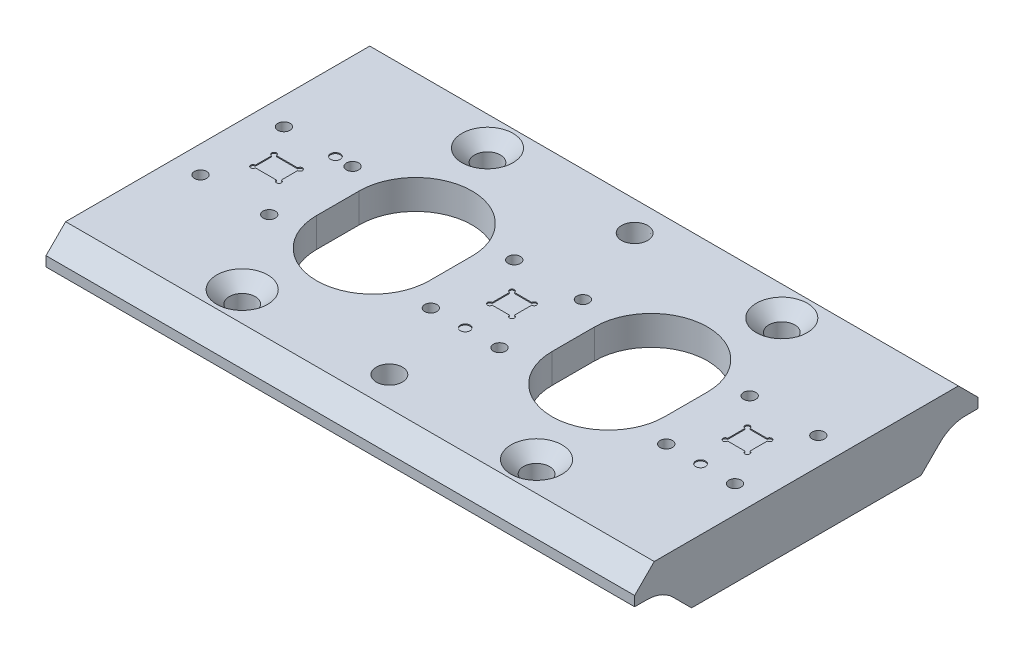
SolidWorks part; units mm, degrees
material "6061 Сплав"
ref_plane "Спереди" through (0, 0, 0) normal (0, 0, 1) x (1, 0, 0)
ref_plane "Сверху" through (0, 0, 0) normal (0, 1, 0) x (1, 0, 0)
ref_plane "Справа" through (0, 0, 0) normal (1, 0, 0) x (0, 0, -1)
sketch "Эскиз5" plane through (0, 0, 0) normal (0, 1, 0) x (1, 0, 0)
  line L1 (0, -35) -> (120, -35)
  line L2 (0, -35) -> (0, 35)
  line L3 (0, 35) -> (120, 35)
  line L4 (120, -35) -> (120, 35)
  line L5 (0, -35) -> (120, 35) construction
  line L6 (0, 35) -> (120, -35) construction
  point P0 (0, 0)
  point P5 (0, 0)
extrude "Бобышка-Вытянуть2" add sketch "Эскиз5" against normal blind 6
ref_axis "Ось1" through (120, 0, 0) along (-1, 0, 0)
sketch "Sketch1" plane through (0, 0, 0) normal (0, 1, 0) x (1, 0, 0)
  line L0 (9.86, -2.16) -> (14.14, -2.16)
  line L1 (9.36, -1.66) -> (9.36, 1.66)
  line L2 (9.86, 2.16) -> (14.14, 2.16)
  line L3 (14.64, -1.66) -> (14.64, 1.66)
  line L4 (9.36, -2.16) -> (14.64, 2.16) construction
  line L5 (9.36, 2.16) -> (14.64, -2.16) construction
  circle A0 centre (16, 8) radius 1
  arc A1 (14.64, 1.66) -> (14.14, 2.16) centre (14.64, 2.16) ccw
  arc A2 (9.86, 2.16) -> (9.36, 1.66) centre (9.36, 2.16) ccw
  arc A3 (9.36, -1.66) -> (9.86, -2.16) centre (9.36, -2.16) ccw
  arc A4 (14.14, -2.16) -> (14.64, -1.66) centre (14.64, -2.16) ccw
  point P0 (0, 0)
  point P1 (12, 0)
  point P2 (12, 0)
  point P9 (5.5, 8)
  point P10 (19.5, 8)
  point P11 (19.5, -9)
  point P12 (5.5, -9)
  dimension "D11" = 5.28
  dimension "D1" = 8
  dimension "D2" = 9
  dimension "D3" = 6.5
  dimension "D4" = 7.5
  dimension "D5" = 6.5
  dimension "D6" = 7.5
  dimension "D7" = 9
  dimension "D8" = 8
  dimension "D9" = 3.5
  dimension "D10" = 8
  dimension "D12" = 4.32
sketch "Sketch2" plane through (0, 0, 0) normal (0, 1, 0) x (1, 0, 0)
  line L0 (24, 35) -> (24, -35) construction
  line L1 (57.74, 1.76) -> (57.74, -1.76)
  line L2 (58.24, 2.26) -> (61.76, 2.26)
  line L3 (62.26, 1.76) -> (62.26, -1.76)
  line L4 (58.24, -2.26) -> (61.76, -2.26)
  line L5 (57.74, 2.26) -> (62.26, -2.26) construction
  line L6 (62.26, 2.26) -> (57.74, -2.26) construction
  line L7 (0, 35) -> (120, 35) construction
  line L8 (0, -35) -> (120, -35) construction
  line L12 (105.74, 1.76) -> (105.74, -1.76)
  line L13 (106.24, 2.26) -> (109.76, 2.26)
  line L14 (110.26, 1.76) -> (110.26, -1.76)
  line L15 (106.24, -2.26) -> (109.76, -2.26)
  line L16 (105.74, 2.26) -> (110.26, -2.26) construction
  line L17 (110.26, 2.26) -> (105.74, -2.26) construction
  circle A0 centre (59.481, -9.027) radius 1
  arc A1 (62.26, 1.76) -> (61.76, 2.26) centre (62.26, 2.26) ccw
  circle A2 centre (107.481, -9.027) radius 1
  arc A3 (58.24, 2.26) -> (57.74, 1.76) centre (57.74, 2.26) ccw
  arc A4 (57.74, -1.76) -> (58.24, -2.26) centre (57.74, -2.26) ccw
  arc A5 (61.76, -2.26) -> (62.26, -1.76) centre (62.26, -2.26) ccw
  arc A6 (110.26, 1.76) -> (109.76, 2.26) centre (110.26, 2.26) ccw
  arc A7 (109.76, -2.26) -> (110.26, -1.76) centre (110.26, -2.26) ccw
  arc A8 (105.74, -1.76) -> (106.24, -2.26) centre (105.74, -2.26) ccw
  arc A9 (106.24, 2.26) -> (105.74, 1.76) centre (105.74, 2.26) ccw
  point P0 (60, 0)
  point P1 (60, 0)
  point P5 (60, 0)
  point P6 (60, 0)
  point P7 (59.481, -9.027)
  point P8 (66.481, -9.027)
  point P9 (52.481, -9.027)
  point P10 (52.481, 7.973)
  point P11 (66.481, 7.973)
  point P31 (108, 0)
  point P32 (108, 0)
  point P36 (108, 0)
  point P37 (108, 0)
  point P38 (107.481, -9.027)
  point P39 (114.481, -9.027)
  point P40 (100.481, -9.027)
  point P41 (100.481, 7.973)
  point P42 (114.481, 7.973)
  dimension "D20" = 4.52
  dimension "D22" = 4.52
  dimension "D24" = 9.027
  dimension "D25" = 0.5
  dimension "D26" = 0.5
  dimension "D1" = 7.519
  dimension "D2" = 6.481
  dimension "D3" = 7.973
  dimension "D4" = 9.027
  dimension "D5" = 7
  dimension "D6" = 7.519
  dimension "D7" = 6.481
  dimension "D8" = 9.027
  dimension "D9" = 7.973
  dimension "D10" = 7.519
  dimension "D11" = 6.481
  dimension "D12" = 7.973
  dimension "D13" = 9.027
  dimension "D14" = 6.481
  dimension "D15" = 7.519
  dimension "D16" = 9.027
  dimension "D17" = 7.973
  dimension "D18" = 7
  dimension "D19" = 9.027
  dimension "D21" = 4.52
  dimension "D23" = 4.52
extrude "Cut-Extrude1" cut sketch "Sketch1" against normal blind 0.2
extrude "Cut-Extrude2" cut sketch "Sketch2" against normal blind 0.2
sketch "Sketch6" plane through (0, 0, 0) normal (0, 1, 0) x (1, 0, 0)
  line L0 (-59.5, 6) -> (150, 6) construction
  line L1 (-59.5, -6) -> (150, -6) construction
  point P4 (36, 6)
  point P5 (60, 6)
  point P6 (84, 6)
  point P7 (84, -6)
  point P8 (60, -6)
  point P9 (36, -6)
sketch "Sketch7" plane through (0, 0, 0) normal (0, 1, 0) x (1, 0, 0)
  line L1 (30, -25) -> (90, -25) construction
  line L2 (30, -25) -> (30, 25) construction
  line L3 (30, 25) -> (90, 25) construction
  line L4 (90, -25) -> (90, 25) construction
  line L5 (30, -25) -> (90, 25) construction
  line L6 (30, 25) -> (90, -25) construction
  point P0 (60, 0)
  point P1 (60, 0)
  point P7 (30, 25)
  point P8 (90, 25)
  point P9 (90, -25)
  point P10 (30, -25)
sketch "Sketch5" plane through (0, -6, 0) normal (0, -1, 0) x (1, 0, 0)
  line L0 (-60, 0) -> (180, 0) construction
  line L1 (60, -25) -> (60, 25) construction
  line L4 (30, 25) -> (90, 25) construction
  line L5 (30, -25) -> (90, -25) construction
  circle A2 centre (60, 25) radius 2.6
  circle A3 centre (60, -25) radius 2.6
  point P6 (60, -25)
  point P7 (45.0651, 0)
  point P8 (60, 0)
  point P9 (60, 25)
  point P11 (60, -25)
  point P16 (84, 0)
  point P17 (60, 25)
  dimension "D1" = 50
hole_wizard "Зенковка для  винта с плоской головкой M51" positions "Sketch9" profile "Sketch8" countersink size "M5" standard "Ansi Metric" end condition through all
sketch "Sketch9" plane through (0, 0, 0) normal (0, 1, 0) x (1, 0, 0)
  point P0 (30, 25)
  point P3 (90, 25)
  point P6 (90, -25)
  point P9 (30, -25)
sketch "Sketch8" plane through (30, 0, -25) normal (1, 0, 0) x (0, 0, 1)
  line L0 (0, 0) -> (0, 6)
  line L1 (0, 6) -> (2.65, 6)
  line L2 (2.65, 6) -> (2.65, 2.55)
  line L3 (2.65, 2.55) -> (5.2, 0)
  line L5 (5.2, 0) -> (0, 0)
  line L6 (-2.65, 2.55) -> (-5.2, 0) construction
  line L11 (0, -6.35) -> (0, 107.95) construction
  dimension "Thru Hole Dia." = 5.3
  dimension "Thru Hole Depth" = 6
  dimension "Near C'Sink Dia." = 10.4
  dimension "Near C'Sink Angle" = 90
extrude "Cut-Extrude4" cut sketch "Sketch5" against normal blind 10 draft 0.573 draft outward yes
sketch "Эскиз6" plane through (0, 0, 0) normal (0, 1, 0) x (1, 0, 0)
  line L19 (24.5, 16.3036) -> (24.5, -16.0342) construction
  line L21 (47.5, 16.3036) -> (47.5, -15.329) construction
  line L23 (72.5, 16.3036) -> (72.5, -16.0342) construction
  line L24 (95.5, 16.3036) -> (95.5, -16.0342) construction
  line L30 (84, 4.35) -> (84, -4.35) construction
  line L31 (95.5, 4.35) -> (95.5, -4.35)
  line L34 (72.5, 4.35) -> (72.5, -4.35)
  line L36 (36, 4.35) -> (36, -4.35) construction
  line L37 (47.5, 4.35) -> (47.5, -4.35)
  line L38 (24.5, 4.35) -> (24.5, -4.35)
  circle A0 centre (60, 25) radius 10 construction
  circle A1 centre (90, 25) radius 10 construction
  circle A2 centre (30, 25) radius 10 construction
  circle A3 centre (30, -25) radius 10 construction
  circle A4 centre (60, -25) radius 10 construction
  circle A5 centre (90, -25) radius 10 construction
  arc A6 (95.5, 4.35) -> (72.5, 4.35) centre (84, 4.35) ccw
  arc A7 (72.5, -4.35) -> (95.5, -4.35) centre (84, -4.35) ccw
  arc A8 (47.5, 4.35) -> (24.5, 4.35) centre (36, 4.35) ccw
  arc A9 (24.5, -4.35) -> (47.5, -4.35) centre (36, -4.35) ccw
  point P0 (60, 25)
  point P6 (60, -25)
  point P8 (60, 0)
  point P37 (12, 0)
  point P67 (84, 0)
  point P81 (36, 0)
  dimension "D3" = 20
  dimension "D1" = 12.5
  dimension "D2" = 12.5
  dimension "D6" = 12.5
  dimension "D7" = 12.5
extrude "Вырез-Вытянуть1" cut sketch "Эскиз6" against normal through all
sketch "Эскиз7" plane through (0, 0, 0) normal (-1, 0, 0) x (0, 0, 1)
  line L0 (-35, -6) -> (35, -6) construction
  line L1 (0, 13.4373) -> (0, -22.9832) construction
  line L2 (-32.5, -13.5) -> (32.5, -13.5) construction
  line L3 (-32.5, -6) -> (32.5, -6)
  line L4 (-23.3934, -12) -> (-27.1967, -8.1967)
  line L5 (23.3934, -12) -> (27.1967, -8.1967)
  line L6 (-23.3934, -12) -> (23.3934, -12)
  arc A0 (-27.1967, -8.1967) -> (-32.5, -6) centre (-32.5, -13.5) ccw
  arc A1 (32.5, -6) -> (27.1967, -8.1967) centre (32.5, -13.5) ccw
  point P10 (0, -13.5)
  dimension "D2" = 15
  dimension "D1" = 65
  dimension "D3" = 45
  dimension "D4" = 6
extrude "Бобышка-Вытянуть3" add sketch "Эскиз7" against normal through all
sketch "Эскиз8" plane through (0, 0, -35) normal (0, 0, -1) x (-1, 0, 0)
  line L0 (-120, -6) -> (0, -6) construction
  line L1 (-106, -41.6197) -> (-14, -41.6197)
  line L2 (-106, -41.6197) -> (-106, -6)
  line L3 (-106, -6) -> (-14, -6)
  line L4 (-14, -41.6197) -> (-14, -6)
  line L5 (-120, -6) -> (-120, 0) construction
  line L6 (0, -6) -> (0, 0) construction
  dimension "D1" = 14
  dimension "D2" = 14
extrude "Вырез-Вытянуть2" cut sketch "Эскиз8" against normal through all
chamfer "Фаска1" distance 4 angle 45 2 edges at (60, 0, -35) (60, 0, 35)
hole_wizard "Отверстие обработанное метчиком M3x0.51" positions "Sketch4" profile "Sketch3" tap size "M3x0.5" standard "Ansi Metric" end condition through all
sketch "Sketch4" plane through (0, 0, 0) normal (0, 1, 0) x (1, 0, 0)
  point P0 (114.481, -9.027)
  point P3 (100.481, -9.027)
  point P6 (100.481, 7.973)
  point P9 (114.481, 7.973)
  point P12 (66.481, 7.973)
  point P15 (52.481, 7.973)
  point P18 (52.481, -9.027)
  point P21 (66.481, -9.027)
  point P24 (19.5, -9)
  point P27 (5.5, -9)
  point P30 (5.5, 8)
  point P33 (19.5, 8)
cosmetic thread "Hole Thread1" parameters "D2"=3
cosmetic thread "Hole Thread2" parameters "D2"=3
cosmetic thread "Hole Thread3" parameters "D2"=3
cosmetic thread "Hole Thread4" parameters "D2"=3
cosmetic thread "Hole Thread5" parameters "D2"=3
cosmetic thread "Hole Thread6" parameters "D2"=3
cosmetic thread "Hole Thread7" parameters "D2"=3
cosmetic thread "Hole Thread8" parameters "D2"=3
cosmetic thread "Hole Thread9" parameters "D2"=3
cosmetic thread "Hole Thread10" parameters "D2"=3
cosmetic thread "Hole Thread11" parameters "D2"=3
cosmetic thread "Hole Thread12" parameters "D2"=3
sketch "Sketch3" plane through (114.481, 0, 9.027) normal (1, 0, 0) x (0, 0, 1)
  line L0 (0, 0) -> (0, 12)
  line L1 (0, 12) -> (1.25, 12)
  line L2 (1.25, 12) -> (1.25, 0)
  line L5 (1.25, 0) -> (0, 0)
  line L11 (0, -6.35) -> (0, 107.95) construction
  dimension "Диаметр проходного сверла" = 2.5
  dimension "Глубина проходного сверла" = 12
